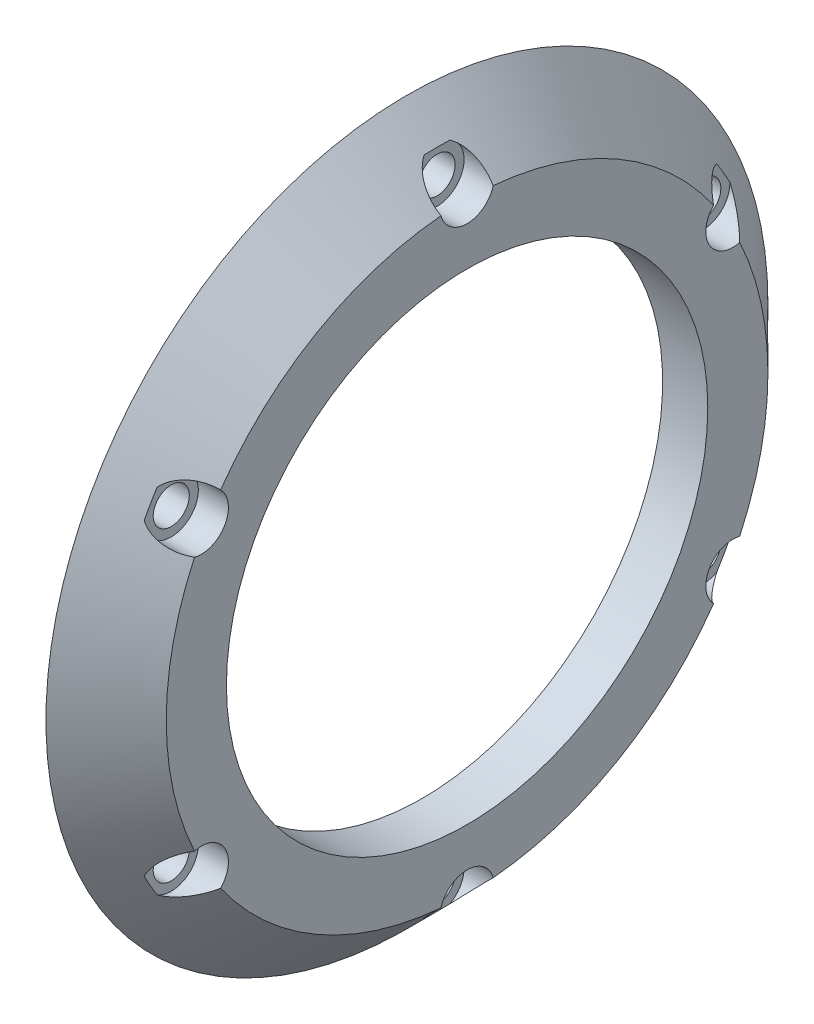
SolidWorks part; units mm, degrees
ref_plane "Alzado" through (0, 0, 0) normal (0, 0, 1) x (1, 0, 0)
ref_plane "Planta" through (0, 0, 0) normal (0, 1, 0) x (1, 0, 0)
ref_plane "Vista lateral" through (0, 0, 0) normal (1, 0, 0) x (0, 0, -1)
sketch "Croquis1" plane through (0, 0, 0) normal (1, 0, 0) x (0, 0, -1)
  line L0 (0, -60) -> (0, 60) construction
  circle A0 centre (0, 0) radius 40
  circle A1 centre (0, 0) radius 60
  circle A2 centre (0, 51) radius 3
  circle A3 centre (44.1673, 25.5) radius 3
  circle A4 centre (44.1673, -25.5) radius 3
  circle A5 centre (0, -51) radius 3
  circle A6 centre (-44.1673, -25.5) radius 3
  circle A7 centre (-44.1673, 25.5) radius 3
  point P7 (0, 0)
  point P22 (0, 0)
  dimension "D1" = 120
  dimension "D2" = 80
  dimension "D4" = 6
  dimension "D3" = 51
  dimension "D5" = 6
extrude "Saliente-Extruir1" add sketch "Croquis1" along normal blind 10
sketch "Croquis2" plane through (0, 0, 0) normal (-1, 0, 0) x (0, 0, 1)
  circle A0 centre (0, 0) radius 47
  dimension "D1" = 94
extrude "Cortar-Extruir1" cut sketch "Croquis2" against normal blind 2.5
chamfer "Chaflán1" distance 10 angle 45 1 edges at (10, 0, -60)
sketch "Croquis5" plane through (10, 0, 0) normal (1, 0, 0) x (0, 0, -1)
  circle A0 centre (0, 51) radius 4.5
  arc A1 (2.7995, 49.9216) -> (-2.7995, 49.9216) centre (0, 51) ccw construction
  circle A2 centre (44.1673, 25.5) radius 4.5
  circle A3 centre (44.1673, -25.5) radius 4.5
  circle A4 centre (0, -51) radius 4.5
  circle A5 centre (-44.1673, -25.5) radius 4.5
  circle A6 centre (-44.1673, 25.5) radius 4.5
  point P18 (0, 0)
  dimension "D2" = 9
  dimension "D1" = 6
extrude "Cortar-Extruir2" cut sketch "Croquis5" against normal blind 5
